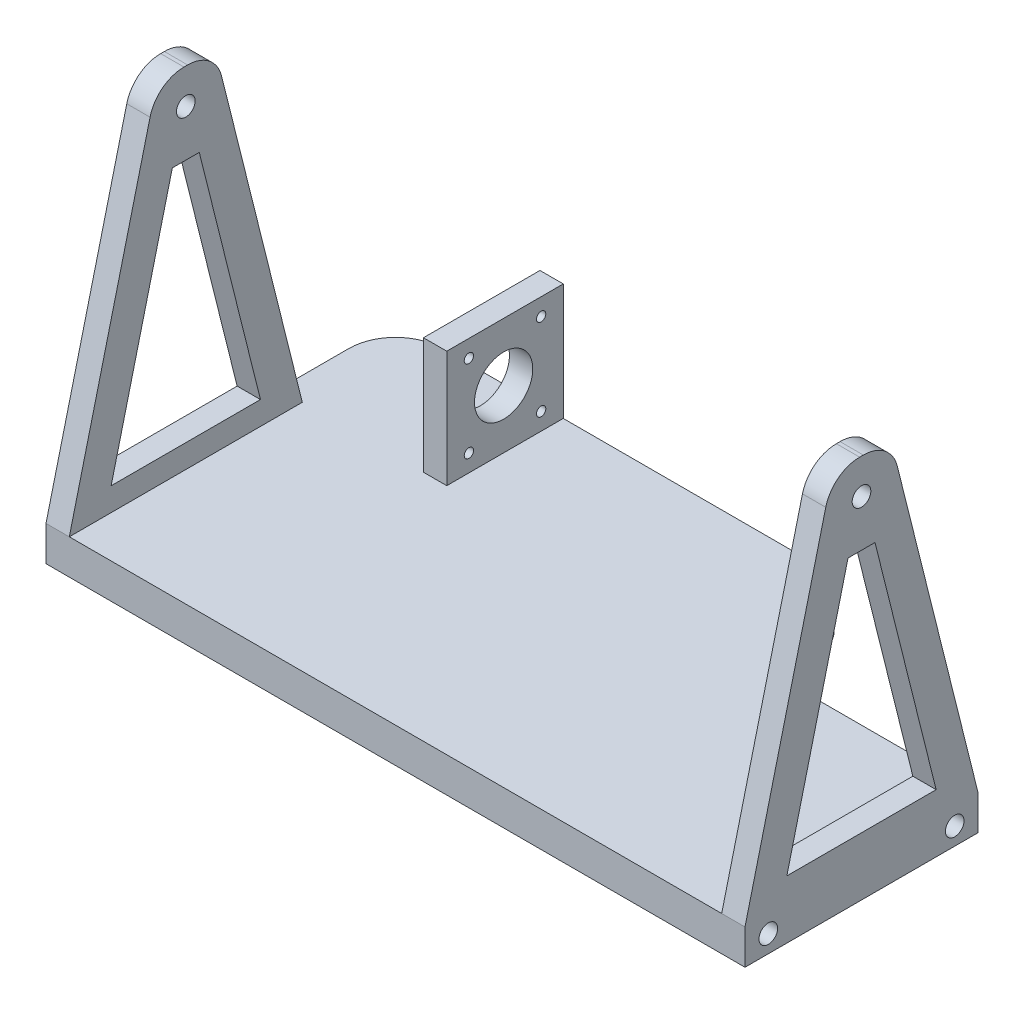
SolidWorks part; units mm, degrees
ref_plane "Front Plane" through (0, 0, 0) normal (0, 0, 1) x (1, 0, 0)
ref_plane "Top Plane" through (0, 0, 0) normal (0, 1, 0) x (1, 0, 0)
ref_plane "Right Plane" through (0, 0, 0) normal (1, 0, 0) x (0, 0, -1)
sketch "Sketch8" plane through (0, 0, 0) normal (0, 1, 0) x (1, 0, 0)
  line L0 (-150, 50) -> (-150, 80)
  line L1 (70, 50) -> (150, 50)
  line L2 (-150, 50) -> (-150, -50)
  line L3 (-150, -50) -> (150, -50)
  line L4 (150, 50) -> (150, -50)
  line L5 (-150, 50) -> (150, -50) construction
  line L6 (-150, -50) -> (150, 50) construction
  line L7 (-130, 100) -> (30, 100)
  line L8 (50, 80) -> (50, 70)
  arc A4 (-150, 80) -> (-130, 100) centre (-130, 80) cw
  arc A5 (30, 100) -> (50, 80) centre (30, 80) cw
  arc A6 (70, 50) -> (50, 70) centre (70, 70) cw
  point P0 (0, 0)
  point P26 (-150, 100)
  point P29 (50, 100)
  dimension "D11" = 20
  dimension "D1" = 100
  dimension "D2" = 300
  dimension "D3" = 50
  dimension "D4" = 200
extrude "Boss-Extrude4" add sketch "Sketch8" along normal blind 15
sketch "Sketch9" plane through (0, 0, 0) normal (1, 0, 0) x (0, 0, -1)
  line L0 (-50, 15) -> (50, 15) construction
  line L1 (0, 55) -> (0, -55) construction
  circle A0 centre (-40, 7.5) radius 4
  circle A1 centre (40, 7.5) radius 4
  dimension "D1" = 8
  dimension "D2" = 7.5
  dimension "D3" = 40
  dimension "D4" = 40
extrude "Cut-Extrude2" cut sketch "Sketch9" against normal through all and the other way through all
sketch "Sketch10" plane through (0, 0, 0) normal (1, 0, 0) x (0, 0, -1)
  line L0 (-50, 15) -> (50, 15)
  line L1 (-0.7884, 165) -> (0.7884, 165)
  line L2 (-50, 15) -> (-15.3405, 153.638)
  line L3 (50, 15) -> (15.3405, 153.638)
  line L4 (0, -13.8594) -> (0, 200.3786) construction
  line L5 (-50, 15) -> (50, 15) construction
  line L6 (0, 55) -> (0, -55) construction
  line L8 (-32.0384, 25) -> (32.0384, 25)
  line L10 (-5.7884, 130) -> (5.7884, 130)
  line L11 (-5.7884, 130) -> (-32.0384, 25)
  line L12 (5.7884, 130) -> (32.0384, 25)
  arc A0 (15.3405, 153.638) -> (0.7884, 165) centre (0.7884, 150) ccw
  arc A1 (-0.7884, 165) -> (-15.3405, 153.638) centre (-0.7884, 150) ccw
  circle A2 centre (0, 150) radius 4
  point P15 (0, 165)
  point P17 (12.5, 165)
  point P20 (-12.5, 165)
  point P27 (0, 25)
  dimension "D3" = 15
  dimension "D4" = 8
  dimension "D1" = 25
  dimension "D2" = 150
  dimension "D5" = 15
  dimension "D7" = 10
  dimension "D8" = 20
extrude "Boss-Extrude6" add sketch "Sketch10" against normal blind 10 from offset 150
sketch "Sketch12" plane through (0, 0, 0) normal (1, 0, 0) x (0, 0, -1)
  line L0 (-50, 15) -> (50, 15)
  line L1 (50, 15) -> (15.3405, 153.638)
  line L2 (0.7884, 165) -> (-0.7884, 165)
  line L3 (-50, 15) -> (-15.3405, 153.638)
  line L4 (-32.0384, 25) -> (32.0384, 25)
  line L5 (32.0384, 25) -> (5.7884, 130)
  line L6 (5.7884, 130) -> (-5.7884, 130)
  line L7 (-5.7884, 130) -> (-32.0384, 25)
  circle A0 centre (0, 150) radius 4
  arc A1 (-15.3405, 153.638) -> (-0.7884, 165) centre (-0.7884, 150) cw
  arc A2 (0.7884, 165) -> (15.3405, 153.638) centre (0.7884, 150) cw
  dimension "D1" = 15
extrude "Boss-Extrude7" add sketch "Sketch12" along normal blind 10 from offset 150 offset against normal yes
ref_axis "Axis5" through (-140, 150, 0) along (-1, 0, 0)
ref_axis "Axis6" through (140, 150, 0) along (1, 0, 0)
ref_axis "Axis7" through (-150, 7.5, 40) along (1, 0, 0)
ref_axis "Axis8" through (-150, 7.5, -40) along (1, 0, 0)
ref_plane "Plane3" through (0, 15, 0) normal (0, 1, 0) x (1, 0, 0)
sketch "Sketch14" plane through (0, 15, 0) normal (0, 1, 0) x (1, 0, 0)
  line L0 (-88, 100) -> (-88, 50)
  line L1 (-88, 50) -> (-78, 50)
  line L2 (-78, 50) -> (-78, 100)
  line L3 (-78, 100) -> (-88, 100)
  line L4 (30, 100) -> (-130, 100) construction
  line L5 (-150, 80) -> (-150, 50) construction
  dimension "D1" = 10
  dimension "D2" = 50
  dimension "D3" = 0
  dimension "D4" = 62
extrude "Boss-Extrude8" add sketch "Sketch14" along normal blind 50
ref_plane "Plane4" through (-88, 0, 0) normal (-1, 0, 0) x (0, 0, 1)
sketch "Sketch15" plane through (-88, 0, 0) normal (-1, 0, 0) x (0, 0, 1)
  line L0 (-75, 77.8178) -> (-75, -10.6516) construction
  line L1 (-114.9479, 40) -> (-33.8716, 40) construction
  line L2 (-100, 65) -> (-50, 65) construction
  line L3 (-100, 65) -> (-100, 15) construction
  circle A0 centre (-90.5, 57.6103) radius 2
  circle A1 centre (-59.5, 57.6103) radius 2
  circle A2 centre (-90.5, 22.3897) radius 2
  circle A3 centre (-59.5, 22.3897) radius 2
  circle A4 centre (-74.4097, 40) radius 12.5
  dimension "D3" = 4
  dimension "D5" = 25
  dimension "D1" = 25
  dimension "D2" = 25
  dimension "D4" = 31
extrude "Cut-Extrude3" cut sketch "Sketch15" against normal blind 10
